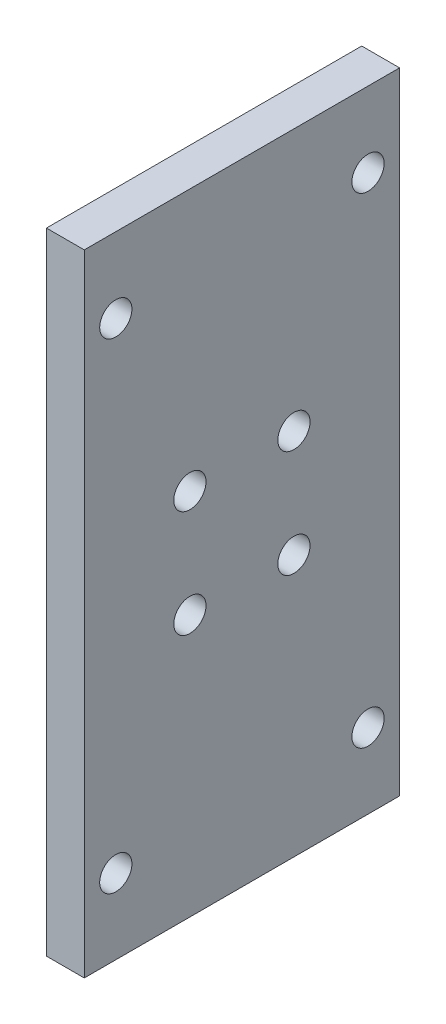
SolidWorks part; units mm, degrees
ref_plane "Front Plane" through (0, 0, 0) normal (1, 0, 0) x (0, 1, 0)
ref_plane "Top Plane" through (0, 0, 0) normal (0, 0, 1) x (0, 1, 0)
ref_plane "Right Plane" through (0, 0, 0) normal (0, 1, 0) x (-1, 0, 0)
sketch "Sketch1" plane through (0, 0, 0) normal (1, 0, 0) x (0, 1, 0)
  line L0 (0, 25) -> (0, -25) construction
  line L1 (-50, -25) -> (50, -25)
  line L2 (-50, -25) -> (-50, 25)
  line L3 (-50, 25) -> (50, 25)
  line L4 (50, -25) -> (50, 25)
  line L5 (-50, -25) -> (50, 25) construction
  line L6 (-50, 25) -> (50, -25) construction
  line L8 (-8.5, -8.25) -> (8.5, -8.25) construction
  line L9 (-8.5, -8.25) -> (-8.5, 8.25) construction
  line L10 (-8.5, 8.25) -> (8.5, 8.25) construction
  line L11 (8.5, -8.25) -> (8.5, 8.25) construction
  line L12 (-8.5, -8.25) -> (8.5, 8.25) construction
  line L13 (-8.5, 8.25) -> (8.5, -8.25) construction
  line L14 (-38.1, -20) -> (38.1, -20) construction
  line L15 (-38.1, -20) -> (-38.1, 20) construction
  line L16 (-38.1, 20) -> (38.1, 20) construction
  line L17 (38.1, -20) -> (38.1, 20) construction
  line L18 (-38.1, -20) -> (38.1, 20) construction
  line L19 (-38.1, 20) -> (38.1, -20) construction
  circle A0 centre (-8.5, 8.25) radius 2.555
  circle A1 centre (-8.5, -8.25) radius 2.555
  circle A2 centre (8.5, -8.25) radius 2.555
  circle A3 centre (8.5, 8.25) radius 2.555
  circle A4 centre (-38.1, 20) radius 2.555
  circle A5 centre (-38.1, -20) radius 2.555
  circle A6 centre (38.1, 20) radius 2.555
  circle A7 centre (38.1, -20) radius 2.555
  point P0 (0, 0)
  point P8 (0, 0)
  point P17 (0, 0)
  dimension "D5" = 5.11
  dimension "D6" = 5.11
  dimension "D9" = 5.11
  dimension "D10" = 5.11
  dimension "D1" = 16.5
  dimension "D2" = 17
  dimension "D3" = 100
  dimension "D4" = 50
  dimension "D7" = 76.2
  dimension "D8" = 40
extrude "Boss-Extrude1" add sketch "Sketch1" along normal blind 6
